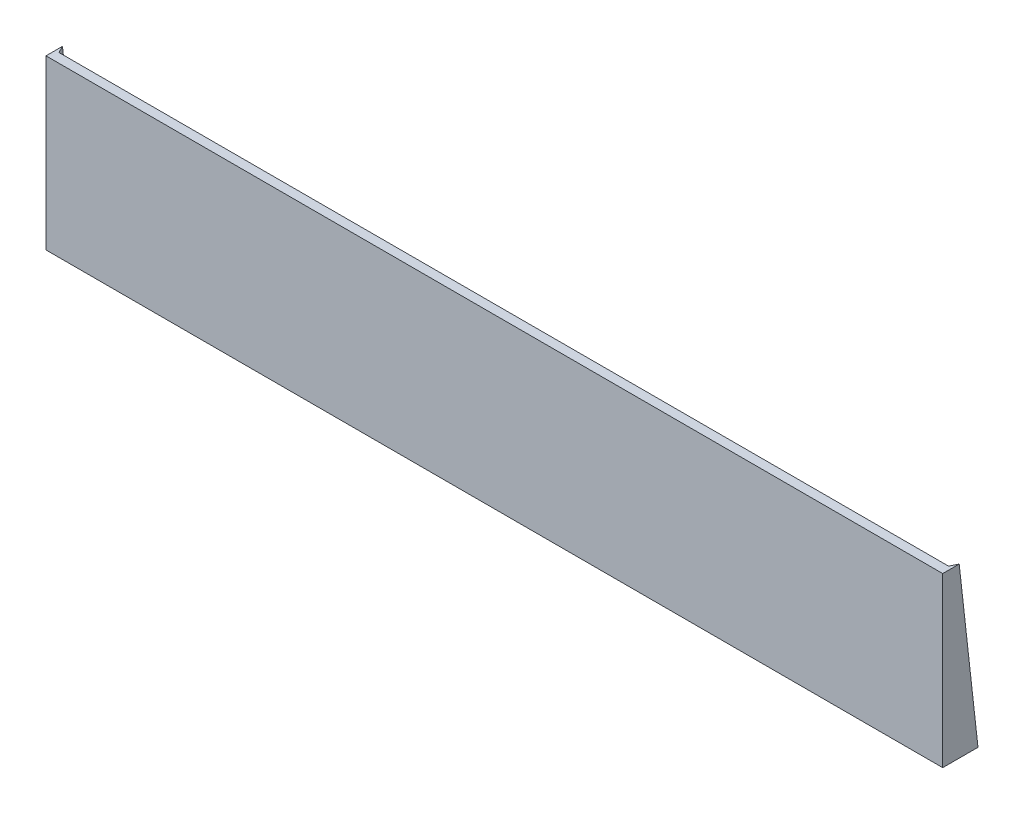
SolidWorks part; units mm, degrees
ref_plane "Front Plane" through (0, 0, 0) normal (0, 0, 1) x (1, 0, 0)
ref_plane "Top Plane" through (0, 0, 0) normal (0, 1, 0) x (1, 0, 0)
ref_plane "Right Plane" through (0, 0, 0) normal (1, 0, 0) x (0, 0, -1)
sketch "Sketch2" plane through (0, 0, 0) normal (0, 1, 0) x (1, 0, 0)
  line L0 (-60.96, 5.08) -> (-59.69, 2.54)
  line L2 (-60.96, 5.08) -> (-60.96, 0)
  line L3 (-60.96, 0) -> (60.96, 0)
  line L4 (60.96, 5.08) -> (60.96, 0)
  line L5 (-59.69, 2.54) -> (59.69, 2.54)
  line L6 (59.69, 2.54) -> (60.96, 5.08)
  point P4 (0, 2.54)
  point P6 (0, 0)
  dimension "D1" = 2.54
  dimension "D2" = 5.08
  dimension "D3" = 1.27
  dimension "D4" = 121.92
extrude "Boss-Extrude1" add sketch "Sketch2" along normal blind 22.86
chamfer "Chamfer1" distance 25.4 distance2 1.27 3 edges at (-60.325, 22.86, -3.81) (0, 22.86, -2.54) (60.325, 22.86, -3.81) first distance on face at (-60.325, 11.43, -3.81) first distance on face at (0, 11.43, -2.54) first distance on face at (60.325, 11.43, -3.81)
